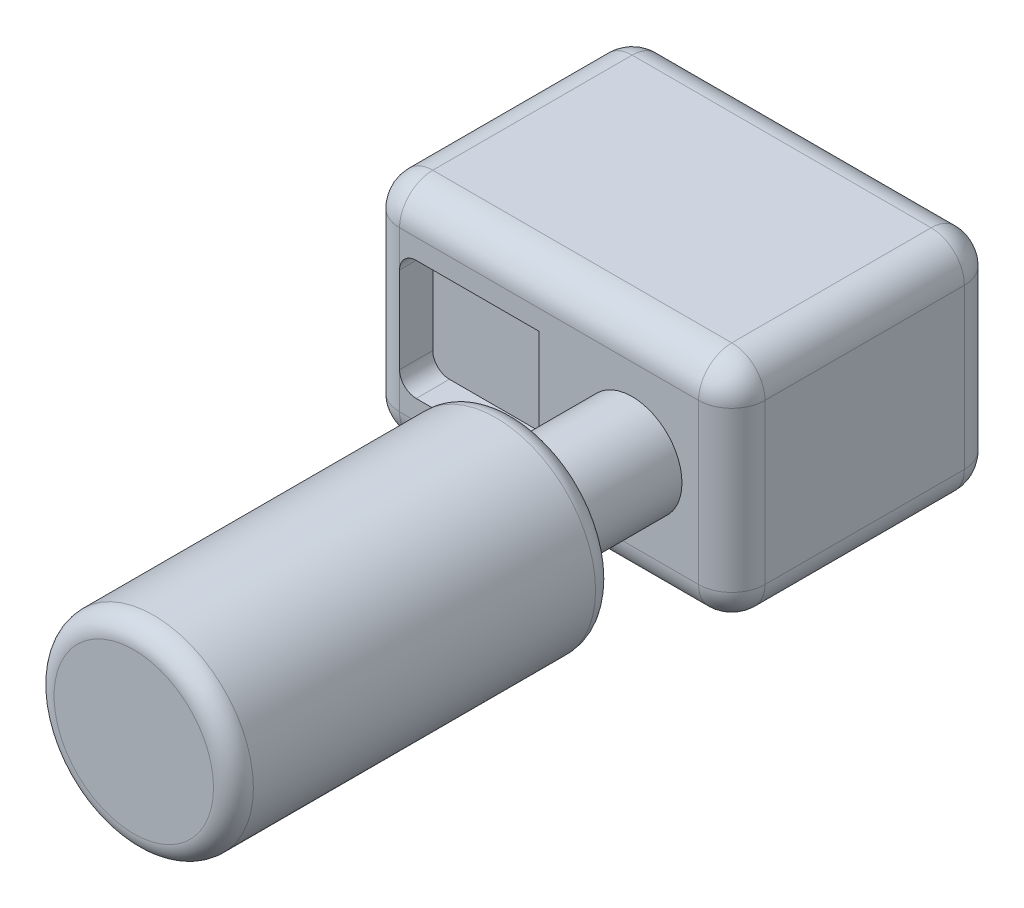
SolidWorks part; units mm, degrees
ref_plane "Plan de face" through (0, 0, 0) normal (0, 0, 1) x (1, 0, 0)
ref_plane "Plan de dessus" through (0, 0, 0) normal (0, 1, 0) x (1, 0, 0)
ref_plane "Plan de droite" through (0, 0, 0) normal (1, 0, 0) x (0, 0, -1)
sketch "Esquisse1" plane through (0, 0, 0) normal (0, 0, 1) x (1, 0, 0)
  line L1 (-33.4925, 48.2749) -> (76.5075, 48.2749)
  line L2 (-33.4925, 48.2749) -> (-33.4925, -19.7251)
  line L3 (-33.4925, -19.7251) -> (76.5075, -19.7251)
  line L4 (76.5075, 48.2749) -> (76.5075, -19.7251)
extrude "Boss.-Extru.1" add sketch "Esquisse1" along normal blind 80
sketch "Esquisse2" plane through (0, 0, 80) normal (0, 0, 1) x (1, 0, 0)
  line L0 (76.5075, 14.2749) -> (-33.4925, 14.2749) construction
  line L1 (-33.4925, 48.2749) -> (76.5075, 48.2749) construction
  line L2 (-33.4925, 48.2749) -> (-33.4925, -19.7251) construction
  line L3 (-33.4925, -19.7251) -> (76.5075, -19.7251) construction
  line L4 (76.5075, 48.2749) -> (76.5075, -19.7251) construction
  circle A0 centre (46.5075, 14.2749) radius 30
extrude "Boss.-Extru.2" add sketch "Esquisse2" along normal blind 150
sketch "Esquisse5" plane through (0, 0, 80) normal (0, 0, 1) x (1, 0, 0)
  line L0 (-33.4925, 14.2749) -> (76.5075, 14.2749) construction
  line L1 (-33.4925, 48.2749) -> (-33.4925, -19.7251) construction
  circle A0 centre (46.5075, 14.2749) radius 30 construction
fillet "Congé2" radius 6 1 edges at (76.5075, 14.2749, 230)
sketch "Esquisse8" plane through (0, 0, 80) normal (0, 0, 1) x (1, 0, 0)
  circle A0 centre (46.5075, 14.2749) radius 30
  circle A1 centre (46.5075, 14.2749) radius 15
extrude "Enlèv. mat.-Extru.1" cut sketch "Esquisse8" along normal blind 35
fillet "Congé3" radius 6 1 edges at (76.5075, 14.2749, 115)
fillet "Congé4" radius 10 11 edges at (76.5075, 14.2749, 0) (76.5075, 48.2749, 40) (21.5075, 48.2749, 0) (21.5075, 48.2749, 80) (-33.4925, 14.2749, 0) (-33.4925, 14.2749, 80) (-33.4925, 48.2749, 40) (-33.4925, -19.7251, 40) (21.5075, -19.7251, 0) (76.5075, -19.7251, 40) (21.5075, -19.7251, 80)
fillet "Congé5" radius 10 3 edges at (73.5785, -16.7962, 77.0711) (73.5785, 45.346, 77.0711) (76.5075, 14.2749, 80)
sketch "Esquisse9" plane through (0, 0, 80) normal (0, 0, 1) x (1, 0, 0)
  line L0 (-26.774, 14.2749) -> (35.8194, 14.2749) construction
  line L1 (-41.6769, 32.2749) -> (35.8194, 32.2749) construction
  line L2 (-41.6769, -3.7251) -> (35.8224, -3.7251) construction
  line L3 (-23.4925, 56.6147) -> (-23.4925, -7.7583) construction
  line L4 (-23.4925, 38.2749) -> (-23.4925, -9.7251) construction
  line L5 (18.5075, 56.6147) -> (18.5075, -7.7583) construction
  line L7 (-18.4925, 32.2749) -> (18.5075, 32.2749)
  line L8 (-23.4925, 27.2749) -> (-23.4925, 1.2749)
  line L9 (-18.4925, -3.7251) -> (18.5075, -3.7251)
  line L10 (18.5075, 32.2749) -> (18.5075, -3.7251)
  arc A0 (-23.4925, 1.2749) -> (-18.4925, -3.7251) centre (-18.4925, 1.2749) ccw
  arc A1 (-18.4925, 32.2749) -> (-23.4925, 27.2749) centre (-18.4925, 27.2749) ccw
  point P20 (-23.4925, 32.2749)
  dimension "D4" = 5
  dimension "D1" = 18
  dimension "D2" = 36
  dimension "D3" = 42
extrude "Enlèv. mat.-Extru.2" cut sketch "Esquisse9" against normal blind 10
